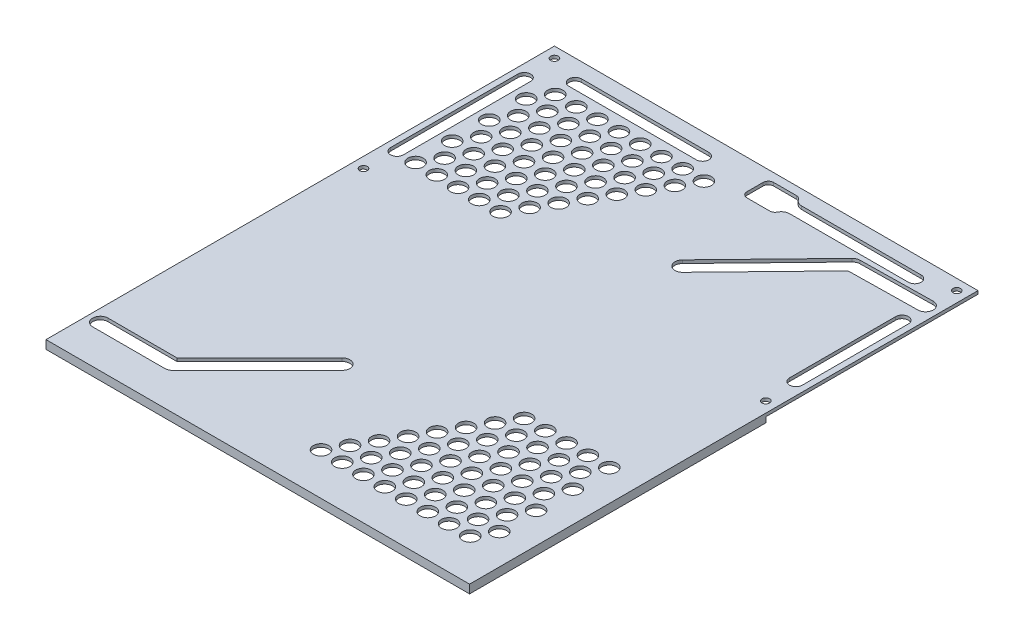
SolidWorks part; units mm, degrees
ref_plane "Front" through (0, 0, 0) normal (0, 0, 1) x (1, 0, 0)
ref_plane "Top" through (0, 0, 0) normal (0, 1, 0) x (1, 0, 0)
ref_plane "Right" through (0, 0, 0) normal (1, 0, 0) x (0, 0, -1)
sketch "Sketch1" plane through (0, 0, 0) normal (0, 1, 0) x (1, 0, 0)
  line L1 (0, 0) -> (126.746, 0)
  line L2 (0, 0) -> (0, 152.146)
  line L3 (0, 152.146) -> (126.746, 152.146)
  line L4 (126.746, 0) -> (126.746, 152.146)
  dimension "D1" = 152.146
  dimension "D2" = 126.746
extrude "Boss-Extrude1" add sketch "Sketch1" along normal blind 2.54
sketch "Sketch2" plane through (0, 2.54, 0) normal (0, 1, 0) x (1, 0, 0)
  line L0 (63.373, 152.146) -> (63.373, 0) construction
  line L1 (126.746, 152.146) -> (0, 152.146) construction
  line L2 (0, 0) -> (126.746, 0) construction
  line L3 (126.746, 76.073) -> (0, 76.073) construction
  line L4 (126.746, 0) -> (126.746, 152.146) construction
  line L5 (0, 152.146) -> (0, 0) construction
  circle A0 centre (63.373, 94.996) radius 1.016
  circle A1 centre (65.913, 94.996) radius 1.016
  circle A2 centre (68.453, 94.996) radius 1.016
  circle A3 centre (70.993, 94.996) radius 1.016
  circle A4 centre (73.533, 94.996) radius 1.016
  circle A5 centre (60.833, 94.996) radius 1.016
  circle A6 centre (58.293, 94.996) radius 1.016
  circle A7 centre (55.753, 94.996) radius 1.016
  circle A8 centre (53.213, 94.996) radius 1.016
  point P14 (63.373, 76.073)
  dimension "D1" = 2.032
  dimension "D4" = 57.15
  dimension "D2" = 5
  dimension "D3" = 5
sketch "Sketch5" plane through (0, 0, 0) normal (0, 1, 0) x (1, 0, 0)
  line L0 (63.373, 152.146) -> (63.373, 0) construction
  line L1 (-0.127, 88.646) -> (126.873, 88.646)
  line L2 (-0.127, 88.646) -> (-0.127, 152.146)
  line L3 (-0.127, 152.146) -> (126.873, 152.146)
  line L4 (126.873, 88.646) -> (126.873, 152.146)
  line L5 (-0.127, 88.646) -> (126.873, 152.146) construction
  line L6 (-0.127, 152.146) -> (126.873, 88.646) construction
  line L7 (126.746, 152.146) -> (0, 152.146) construction
  point P0 (63.373, 120.396)
  dimension "D1" = 63.5
  dimension "D2" = 127
extrude "Cut-Extrude2" cut sketch "Sketch5" along normal blind 1.5875
sketch "Sketch9" plane through (0, 2.54, 0) normal (0, 1, 0) x (1, 0, 0)
  line L0 (50.673, 37.973) -> (25.273, 12.573) construction
  line L1 (52.2894, 36.3566) -> (26.8894, 10.9566)
  line L2 (49.0566, 39.5894) -> (23.6566, 14.1894)
  line L3 (25.273, 12.573) -> (3.683, 12.573) construction
  line L4 (25.273, 10.287) -> (3.683, 10.287)
  line L5 (25.273, 14.859) -> (3.683, 14.859)
  line L6 (63.373, 152.146) -> (63.373, 0) construction
  line L7 (126.746, 76.073) -> (0, 76.073) construction
  line L8 (76.2, 114.3) -> (101.2059, 140.0881) construction
  line L9 (74.5589, 115.8914) -> (99.5647, 141.6795)
  line L10 (77.8411, 112.7086) -> (102.847, 138.4967)
  line L11 (101.2059, 140.0881) -> (122.7933, 140.4205) construction
  line L12 (101.1707, 142.3738) -> (122.7581, 142.7063)
  line L13 (101.2411, 137.8024) -> (122.8285, 138.1348)
  arc A0 (52.2894, 36.3566) -> (49.0566, 39.5894) centre (50.673, 37.973) ccw
  arc A1 (23.6566, 14.1894) -> (26.8894, 10.9566) centre (25.273, 12.573) ccw
  arc A2 (25.273, 10.287) -> (25.273, 14.859) centre (25.273, 12.573) ccw
  arc A3 (3.683, 14.859) -> (3.683, 10.287) centre (3.683, 12.573) ccw
  arc A4 (74.5589, 115.8914) -> (77.8411, 112.7086) centre (76.2, 114.3) ccw
  arc A5 (102.847, 138.4967) -> (99.5647, 141.6795) centre (101.2059, 140.0881) ccw
  arc A6 (101.1707, 142.3738) -> (101.2411, 137.8024) centre (101.2059, 140.0881) ccw
  arc A7 (122.8285, 138.1348) -> (122.7581, 142.7063) centre (122.7933, 140.4205) ccw
  point P2 (37.973, 25.273)
  point P7 (14.478, 12.573)
  point P23 (88.7029, 127.194)
  point P28 (111.9996, 140.2543)
  point P35 (63.7303, 76.0382)
  dimension "D1" = 2.286
  dimension "D2" = 2.286
  dimension "D3" = 12.7
  dimension "D4" = 38.1
  dimension "D5" = 38.1
  dimension "D6" = 63.5
  dimension "D7" = 59.69
  dimension "D8" = 2
extrude "Cut-Extrude5" cut sketch "Sketch9" against normal through all contours A6 L9 A4 L10 L13 | A5 A6 L13 L10 | L13 A7 L12 A5 L10 | A2 L1 A0 L2 L5 | A1 A2 L5 L2 | L5 A3 L4 A1 L2 region at (39.2527, 2.54, -26.5507) region at (25.2669, 2.54, -12.5876) region at (12.6692, 2.54, -12.5706) region at (87.443, 2.54, -125.8968) region at (101.2122, 2.54, -140.0736) region at (113.8081, 2.54, -140.2846)
sketch "Sketch10" plane through (0, 2.54, 0) normal (0, 1, 0) x (1, 0, 0)
  line L0 (126.746, 76.073) -> (0, 76.073) construction
  line L1 (63.373, 152.146) -> (63.373, 0) construction
  circle A1 centre (82.423, 12.573) radius 2.286
  circle A2 centre (85.6007, 18.0769) radius 2.286
  circle A3 centre (88.7783, 23.5808) radius 2.286
  circle A4 centre (91.956, 29.0847) radius 2.286
  circle A5 centre (95.1337, 34.5886) radius 2.286
  circle A6 centre (98.3114, 40.0925) radius 2.286
  circle A7 centre (101.489, 45.5964) radius 2.286
  circle A8 centre (104.6667, 51.1003) radius 2.286
  circle A9 centre (91.9975, 18.0769) radius 2.286
  circle A10 centre (95.1751, 23.5808) radius 2.286
  circle A11 centre (98.3528, 29.0847) radius 2.286
  circle A12 centre (101.5305, 34.5886) radius 2.286
  circle A13 centre (104.7082, 40.0925) radius 2.286
  circle A14 centre (107.8858, 45.5964) radius 2.286
  circle A15 centre (111.0635, 51.1003) radius 2.286
  circle A16 centre (88.8198, 12.573) radius 2.286
  circle A17 centre (98.3942, 18.0769) radius 2.286
  circle A18 centre (101.5719, 23.5808) radius 2.286
  circle A19 centre (104.7496, 29.0847) radius 2.286
  circle A20 centre (107.9273, 34.5886) radius 2.286
  circle A21 centre (111.1049, 40.0925) radius 2.286
  circle A22 centre (114.2826, 45.5964) radius 2.286
  circle A23 centre (117.4603, 51.1003) radius 2.286
  circle A24 centre (95.2166, 12.573) radius 2.286
  circle A25 centre (101.6835, 12.573) radius 2.286
  circle A26 centre (104.8612, 18.0769) radius 2.286
  circle A27 centre (108.0389, 23.5808) radius 2.286
  circle A28 centre (111.2166, 29.0847) radius 2.286
  circle A29 centre (114.3942, 34.5886) radius 2.286
  circle A30 centre (117.5719, 40.0925) radius 2.286
  circle A31 centre (108.0335, 12.573) radius 2.286
  circle A32 centre (111.2112, 18.0769) radius 2.286
  circle A33 centre (114.3889, 23.5808) radius 2.286
  circle A34 centre (117.5666, 29.0847) radius 2.286
  circle A35 centre (114.3835, 12.573) radius 2.286
  circle A36 centre (117.5612, 18.0769) radius 2.286
  circle A37 centre (44.6443, 139.5299) radius 2.286
  circle A38 centre (41.4355, 134.0441) radius 2.286
  circle A39 centre (38.2266, 128.5583) radius 2.286
  circle A40 centre (35.0178, 123.0725) radius 2.286
  circle A41 centre (31.8089, 117.5867) radius 2.286
  circle A42 centre (28.6001, 112.1009) radius 2.286
  circle A43 centre (25.3913, 106.6152) radius 2.286
  circle A44 centre (22.1824, 101.1294) radius 2.286
  circle A45 centre (35.0388, 134.0804) radius 2.286
  circle A46 centre (31.8299, 128.5946) radius 2.286
  circle A47 centre (28.6211, 123.1088) radius 2.286
  circle A48 centre (25.4123, 117.623) radius 2.286
  circle A49 centre (22.2034, 112.1372) radius 2.286
  circle A50 centre (18.9946, 106.6514) radius 2.286
  circle A51 centre (15.7858, 101.1656) radius 2.286
  circle A52 centre (38.2476, 139.5661) radius 2.286
  circle A53 centre (28.6421, 134.1166) radius 2.286
  circle A54 centre (25.4333, 128.6308) radius 2.286
  circle A55 centre (22.2244, 123.1451) radius 2.286
  circle A56 centre (19.0156, 117.6593) radius 2.286
  circle A57 centre (15.8067, 112.1735) radius 2.286
  circle A58 centre (12.5979, 106.6877) radius 2.286
  circle A59 centre (9.3891, 101.2019) radius 2.286
  circle A60 centre (31.8509, 139.6024) radius 2.286
  circle A61 centre (25.3841, 139.6391) radius 2.286
  circle A62 centre (22.1752, 134.1533) radius 2.286
  circle A63 centre (18.9664, 128.6675) radius 2.286
  circle A64 centre (15.7576, 123.1817) radius 2.286
  circle A65 centre (12.5487, 117.696) radius 2.286
  circle A66 centre (9.3399, 112.2102) radius 2.286
  circle A67 centre (19.0342, 139.6751) radius 2.286
  circle A68 centre (15.8253, 134.1893) radius 2.286
  circle A69 centre (12.6165, 128.7035) radius 2.286
  circle A70 centre (9.4077, 123.2177) radius 2.286
  circle A71 centre (12.6843, 139.7111) radius 2.286
  circle A72 centre (9.4754, 134.2253) radius 2.286
  circle A73 centre (76.073, 12.573) radius 2.286
  circle A74 centre (79.2507, 18.0769) radius 2.286
  circle A75 centre (82.4283, 23.5808) radius 2.286
  circle A76 centre (85.606, 29.0847) radius 2.286
  circle A77 centre (88.7837, 34.5886) radius 2.286
  circle A78 centre (91.9614, 40.0925) radius 2.286
  circle A79 centre (95.139, 45.5964) radius 2.286
  circle A80 centre (98.3167, 51.1003) radius 2.286
  circle A81 centre (69.723, 12.573) radius 2.286
  circle A82 centre (72.9007, 18.0769) radius 2.286
  circle A83 centre (76.0783, 23.5808) radius 2.286
  circle A84 centre (79.256, 29.0847) radius 2.286
  circle A85 centre (82.4337, 34.5886) radius 2.286
  circle A86 centre (85.6114, 40.0925) radius 2.286
  circle A87 centre (88.789, 45.5964) radius 2.286
  circle A88 centre (91.9667, 51.1003) radius 2.286
  circle A89 centre (28.5324, 101.1294) radius 2.286
  circle A90 centre (31.7413, 106.6152) radius 2.286
  circle A91 centre (34.9501, 112.1009) radius 2.286
  circle A92 centre (38.1589, 117.5867) radius 2.286
  circle A93 centre (41.3678, 123.0725) radius 2.286
  circle A94 centre (44.5766, 128.5583) radius 2.286
  circle A95 centre (47.7855, 134.0441) radius 2.286
  circle A96 centre (50.9943, 139.5299) radius 2.286
  circle A97 centre (34.8824, 101.1294) radius 2.286
  circle A98 centre (38.0913, 106.6152) radius 2.286
  circle A99 centre (41.3001, 112.1009) radius 2.286
  circle A100 centre (44.5089, 117.5867) radius 2.286
  circle A101 centre (47.7178, 123.0725) radius 2.286
  circle A102 centre (50.9266, 128.5583) radius 2.286
  circle A103 centre (54.1355, 134.0441) radius 2.286
  circle A104 centre (57.3443, 139.5299) radius 2.286
  point P151 (63.3536, 75.9979)
  dimension "D1" = 3
  dimension "D3" = 2
  dimension "D4" = 4.572
  dimension "D5" = 63.5
  dimension "D6" = 19.05
  dimension "D2" = 2
  dimension "D7" = 8
  dimension "D8" = 2
  dimension "D10" = 3
  dimension "D11" = 3
  dimension "D9" = 2
extrude "Cut-Extrude6" cut sketch "Sketch10" against normal through all
sketch "Sketch12" plane through (0, 2.54, 0) normal (0, 1, 0) x (1, 0, 0)
  line L0 (76.073, 145.796) -> (114.173, 145.796) construction
  line L1 (76.073, 147.701) -> (114.173, 147.701)
  line L2 (76.073, 143.891) -> (114.173, 143.891)
  line L3 (63.373, 152.146) -> (63.373, 0) construction
  line L4 (63.373, 152.146) -> (63.373, 135.3884) construction
  line L5 (50.673, 145.796) -> (12.573, 145.796) construction
  line L6 (50.673, 147.701) -> (12.573, 147.701)
  line L7 (50.673, 143.891) -> (12.573, 143.891)
  line L8 (3.683, 139.446) -> (3.683, 101.346) construction
  line L9 (5.588, 139.446) -> (5.588, 101.346)
  line L10 (1.778, 139.446) -> (1.778, 101.346)
  line L11 (126.746, 152.146) -> (0, 152.146) construction
  arc A0 (76.073, 147.701) -> (76.073, 143.891) centre (76.073, 145.796) ccw
  arc A1 (114.173, 143.891) -> (114.173, 147.701) centre (114.173, 145.796) ccw
  arc A2 (50.673, 147.701) -> (50.673, 143.891) centre (50.673, 145.796) cw
  arc A3 (12.573, 143.891) -> (12.573, 147.701) centre (12.573, 145.796) cw
  arc A4 (5.588, 139.446) -> (1.778, 139.446) centre (3.683, 139.446) ccw
  arc A5 (1.778, 101.346) -> (5.588, 101.346) centre (3.683, 101.346) ccw
  point P2 (95.123, 145.796)
  point P14 (31.623, 145.796)
  point P21 (3.683, 120.396)
  dimension "D1" = 3.81
  dimension "D2" = 38.1
  dimension "D3" = 50.8
  dimension "D4" = 3.81
  dimension "D5" = 12.7
  dimension "D6" = 38.1
  dimension "D7" = 59.69
  dimension "D8" = 6.35
extrude "Cut-Extrude7" cut sketch "Sketch12" against normal through all and the other way through all
sketch "Sketch13" plane through (0, 0, 0) normal (0, -1, 0) x (1, 0, 0)
  line L0 (52.2894, -39.5894) -> (14.4021, -1.7021) construction
  line L1 (1.397, -12.573) -> (44.5875, -12.573) construction
  line L2 (49.0566, -39.5894) -> (52.2894, -36.3566) construction
  line L3 (3.683, -14.859) -> (3.683, -10.287) construction
  line L4 (50.673, -37.973) -> (25.273, -12.573) construction
  line L5 (47.3054, -41.3406) -> (21.9054, -15.9406)
  line L6 (54.0406, -34.6054) -> (28.6406, -9.2054)
  line L7 (25.273, -12.573) -> (3.683, -12.573) construction
  line L8 (25.273, -17.3355) -> (3.683, -17.3355)
  line L9 (25.273, -7.8105) -> (3.683, -7.8105)
  arc A0 (49.0566, -39.5894) -> (52.2894, -36.3566) centre (50.673, -37.973) ccw construction
  arc A1 (3.683, -10.287) -> (3.683, -14.859) centre (3.683, -12.573) ccw construction
  arc A2 (47.3054, -41.3406) -> (54.0406, -34.6054) centre (50.673, -37.973) ccw
  arc A3 (28.6406, -9.2054) -> (21.9054, -15.9406) centre (25.273, -12.573) ccw
  arc A4 (25.273, -17.3355) -> (25.273, -7.8105) centre (25.273, -12.573) ccw
  arc A5 (3.683, -7.8105) -> (3.683, -17.3355) centre (3.683, -12.573) ccw
  point P18 (25.273, -12.573)
  point P21 (37.973, -25.273)
  point P28 (14.478, -12.573)
  dimension "D1" = 9.525
  dimension "D2" = 9.525
extrude "Cut-Extrude8" cut sketch "Sketch13" against normal blind 1.5875 contours A4 L8 L5 A2 L6 | L8 A4 A3 L5 | L9 A5 L8 L5 A3 region at (40.6425, 0, -27.9334) region at (10.7074, 0, -12.5624) region at (25.2604, 0, -12.6034)
sketch "Sketch14" plane through (0, 0, 0) normal (0, -1, 0) x (1, 0, 0)
  line L0 (117.4603, -48.8143) -> (117.4603, -53.3863) construction
  line L1 (117.4603, -53.3863) -> (119.7463, -51.1003) construction
  line L2 (119.7463, -51.1003) -> (115.1743, -51.1003) construction
  line L3 (87.8423, -53.4815) -> (65.5986, -14.9542)
  line L4 (69.723, -7.8105) -> (114.3835, -7.8105)
  line L5 (91.9667, -55.8628) -> (117.4603, -55.8628)
  line L6 (118.6366, -10.43) -> (121.4784, -15.3681)
  line L7 (122.2228, -51.1148) -> (122.3237, -18.0914)
  circle A0 centre (69.723, -12.573) radius 4.7625
  circle A1 centre (91.9667, -51.1003) radius 4.7625
  circle A2 centre (114.3835, -12.573) radius 4.7625
  circle A3 centre (117.4603, -51.1003) radius 2.286 construction
  circle A4 centre (117.4603, -51.1003) radius 4.7625
  circle A5 centre (117.5612, -18.0769) radius 4.7625
  dimension "D1" = 9.525
  dimension "D2" = 9.525
  dimension "D3" = 9.525
  dimension "D4" = 9.525
  dimension "D5" = 9.525
extrude "Cut-Extrude9" cut sketch "Sketch14" against normal blind 1.5875 contours A5 A2 L4 A0 L3 A1 L5 A4 L7 | A0 | A5 A2 | A5 A2 | A4 | A1 | A2 A5 | A5 L6 A2 region at (97.3993, 0, -29.7642) region at (91.9667, 0, -51.1003) region at (69.723, 0, -12.573) region at (117.4603, 0, -51.1003) region at (113.9391, 0, -11.8033) region at (119.7759, 0, -13.1183) region at (115.9724, 0, -15.3249) region at (118.0056, 0, -18.8466)
sketch "Sketch15" plane through (0, 2.54, 0) normal (0, 1, 0) x (1, 0, 0)
  line L0 (126.746, 152.146) -> (0, 152.146) construction
  line L1 (0, 152.146) -> (0, 0) construction
  line L2 (63.373, 152.146) -> (63.373, 127.0009) construction
  circle A0 centre (3.175, 148.971) radius 1.1303
  circle A1 centre (3.175, 91.821) radius 1.1303
  circle A2 centre (123.571, 91.821) radius 1.1303
  circle A3 centre (123.571, 148.971) radius 1.1303
  dimension "D1" = 2.2606
  dimension "D2" = 3.175
  dimension "D3" = 3.175
  dimension "D4" = 2
extrude "Cut-Extrude10" cut sketch "Sketch15" against normal through all
sketch "Sketch16" plane through (0, 2.54, 0) normal (0, 1, 0) x (1, 0, 0)
  line L0 (123.063, 101.346) -> (123.063, 133.096) construction
  line L1 (121.158, 101.346) -> (121.158, 133.096)
  line L2 (124.968, 101.346) -> (124.968, 133.096)
  line L3 (63.373, 152.146) -> (63.373, 0) construction
  line L4 (126.746, 152.146) -> (0, 152.146) construction
  arc A0 (121.158, 101.346) -> (124.968, 101.346) centre (123.063, 101.346) ccw
  arc A1 (124.968, 133.096) -> (121.158, 133.096) centre (123.063, 133.096) ccw
  point P2 (123.063, 117.221)
  dimension "D1" = 1.905
  dimension "D2" = 59.69
  dimension "D3" = 31.75
  dimension "D4" = 19.05
extrude "Cut-Extrude11" cut sketch "Sketch16" against normal through all
sketch "Sketch17" plane through (0, 2.54, 0) normal (0, 1, 0) x (1, 0, 0)
  line L0 (126.746, 152.146) -> (0, 152.146) construction
  line L1 (74.9605, 149.606) -> (68.1355, 149.606)
  line L2 (76.548, 148.0185) -> (76.548, 143.1935)
  line L3 (74.9605, 141.606) -> (68.1355, 141.606)
  line L4 (66.548, 148.0185) -> (66.548, 143.1935)
  line L5 (63.373, 152.146) -> (63.373, 0) construction
  arc A0 (74.9605, 149.606) -> (76.548, 148.0185) centre (74.9605, 148.0185) cw
  arc A1 (76.548, 143.1935) -> (74.9605, 141.606) centre (74.9605, 143.1935) cw
  arc A2 (68.1355, 141.606) -> (66.548, 143.1935) centre (68.1355, 143.1935) cw
  arc A3 (68.1355, 149.606) -> (66.548, 148.0185) centre (68.1355, 148.0185) ccw
  point P10 (76.548, 149.606)
  point P15 (66.548, 141.606)
  point P18 (66.548, 149.606)
  dimension "D5" = 1.5875
  dimension "D1" = 8
  dimension "D2" = 10
  dimension "D3" = 2.54
  dimension "D4" = 3.175
extrude "Cut-Extrude12" cut sketch "Sketch17" against normal through all
fillet "Fillet1" radius 2.54 2 edges at (76.548, 2.0638, -147.701) (76.548, 2.0638, -143.891)
